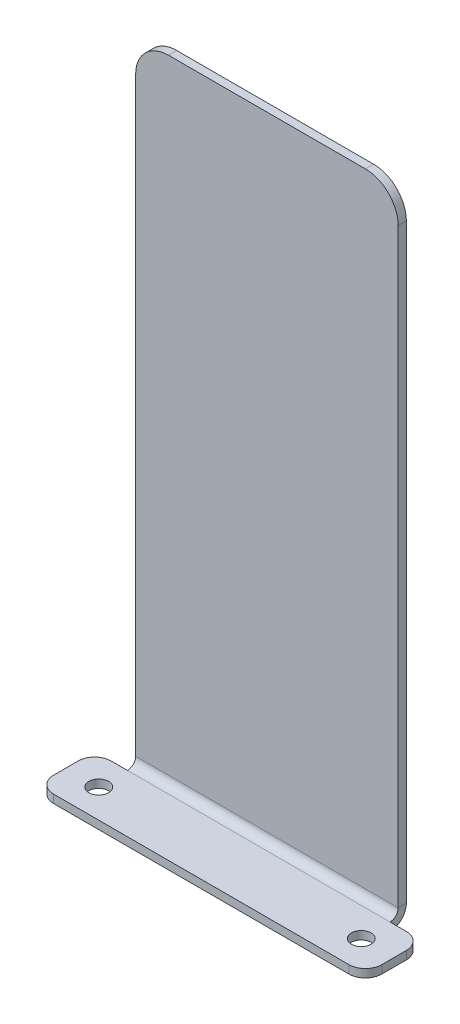
SolidWorks part; units mm, degrees
note: The reader was unsure of these and kept them because the rebuilt part matched: thickness of "Base-Flange1", "Edge-Flange1", "Sheet-Metal1", "Sheet-Metal2", "Sheet-Metal3", "Sheet-Metal4"; flange length of "Edge-Flange1".
material "5052-H32"
ref_plane "Front Plane" through (0, 0, 0) normal (0, 0, 1) x (1, 0, 0)
ref_plane "Top Plane" through (0, 0, 0) normal (0, 1, 0) x (1, 0, 0)
ref_plane "Right Plane" through (0, 0, 0) normal (1, 0, 0) x (0, 0, -1)
sketch "Sketch1" plane through (0, 0, 0) normal (0, 0, 1) x (1, 0, 0)
  line L1 (-50.8, 0) -> (50.8, 0)
  line L2 (-50.8, 0) -> (-50.8, 247.65)
  line L3 (-50.8, 247.65) -> (50.8, 247.65)
  line L4 (50.8, 0) -> (50.8, 247.65)
  point P4 (0, 0)
  dimension "D1" = 101.6
  dimension "D2" = 247.65
base flange "Base-Flange1" sketch "Sketch1" thickness 3.175 reverse thickness direction no parameters "D1"=3.175
edge flange "Edge-Flange1" sketch "Sketch8" flange angle 90 flange length 25.4 flange position material inside bend radius 3.175 thickness 3.175 relief rectangular parameters "D1"=3.9688, "D6"=10
sketch "Sketch8" plane through (0, 0, 0) normal (0, -1, 0) x (1, 0, 0)
  line L0 (-50.8, 0) -> (50.8, 0) construction
  line L1 (-50.8, 0) -> (50.8, 0)
  line L2 (-50.8, 0) -> (-50.8, 25.4)
  line L3 (-50.8, 25.4) -> (50.8, 25.4)
  line L4 (50.8, 25.4) -> (50.8, 0)
bend "EdgeBend1" bend radius 3.175 bend angle 90 parameters "D5"=1
fillet "Fillet1" radius 12.7 2 edges at (-50.8, 247.65, -1.5875) (50.8, 247.65, -1.5875)
sketch "Sketch9" plane through (0, 3.175, 0) normal (0, 1, 0) x (1, 0, 0)
  line L0 (-50.8, -3.175) -> (50.8, -3.175) construction
  line L1 (-63.5, -25.4) -> (63.5, -25.4)
  line L2 (-63.5, -25.4) -> (-63.5, -3.175)
  line L3 (-63.5, -3.175) -> (63.5, -3.175)
  line L4 (63.5, -25.4) -> (63.5, -3.175)
  line L5 (50.8, -25.4) -> (-50.8, -25.4) construction
  line L6 (-50.8, -25.4) -> (-50.8, -3.175) construction
  point P8 (0, -25.4)
  dimension "D1" = 12.7
extrude "Boss-Extrude1" add sketch "Sketch9" against normal up to surface (3.175 mm away) up to face at (0, 0, 14.2875)
sketch "Sketch10" plane through (0, 3.175, 0) normal (0, 1, 0) x (1, 0, 0)
  line L0 (-50.8, -14.2875) -> (50.8, -14.2875) construction
  line L1 (-50.8, -3.175) -> (-63.5, -3.175) construction
  point P2 (0, -14.2875)
  dimension "D1" = 11.1125
  dimension "D2" = 101.6
hole_wizard "1/4 Clearance Hole1" positions "Sketch11" profile "Sketch12" hole size "1/4" standard "ANSI Inch" end condition through all
sketch "Sketch11" plane through (0, 3.175, 0) normal (0, 1, 0) x (1, 0, 0)
  point P0 (-50.8, -14.2875)
  point P3 (50.8, -14.2875)
sketch "Sketch12" plane through (-50.8, 3.175, 14.2875) normal (1, 0, 0) x (0, 0, 1)
  line L0 (0, 0) -> (0, 3.175)
  line L1 (0, 3.175) -> (3.81, 3.175)
  line L2 (3.81, 3.175) -> (3.81, 0)
  line L5 (3.81, 0) -> (0, 0)
  line L11 (0, -6.35) -> (0, 107.95) construction
  dimension "Thru Hole Dia." = 7.62
  dimension "Thru Hole Depth" = 3.175
fillet "Fillet3" radius 6.35 4 edges at (-63.5, 1.5875, 3.175) (-63.5, 1.5875, 25.4) (63.5, 1.5875, 3.175) (63.5, 1.5875, 25.4)
sketch "Bend-Lines1" [suppressed] plane through (0, 0, 0) normal (0, 1, 0) x (1, 0, 0)
sketch "Bounding-Box1" [suppressed] plane through (0, 0, 0) normal (0, 1, 0) x (1, 0, 0)
sheet metal parameters "Sheet-Metal1" thickness 3.175 parameters "D1"=2.9766, "D7"=1.9844
flat pattern "Flat-Pattern1" [suppressed]
sketch "Bend-Lines2" plane through (0, 0, 0) normal (0, 1, 0) x (1, 0, 0)
sketch3d "Bounding-Box2" [suppressed]
  line L0 (-50.8, 241.3, 0) -> (-50.8, 0, 0) construction
  line L1 (50.8, 241.3, 0) -> (50.8, 0, 0) construction
  line L2 (-50.8, 241.3, 0) -> (50.8, 241.3, 0) construction
  line L3 (-50.8, 0, 0) -> (50.8, 0, 0) construction
sheet metal parameters "Sheet-Metal2" thickness 3.175 parameters "D1"=2.9766, "D7"=1.9844
flat pattern "Flat-Pattern1"
sketch "Bend-Lines2" plane through (0, 0, 0) normal (0, 0, 1) x (1, 0, 0)
  line L0 (-50.8, 1.8439) -> (50.8, 1.8439) construction
  line L1 (-50.8, 1.8439) -> (50.8, 1.8439) construction
sketch3d "Bounding-Box2" [suppressed]
  line L0 (50.8, -36.3966, 0) -> (50.8, 247.65, 0) construction
  line L1 (-50.8, -36.3966, 0) -> (-50.8, 247.65, 0) construction
  line L2 (50.8, -36.3966, 0) -> (-50.8, -36.3966, 0) construction
  line L3 (50.8, 247.65, 0) -> (-50.8, 247.65, 0) construction
bend of the flat pattern "Flatten-<EdgeBend1>1"
sheet metal parameters "Sheet-Metal3" thickness 3.175 parameters "D1"=2.9766, "D7"=1.9844
flat pattern "Flat-Pattern1"
sketch "Bend-Lines2" plane through (0, 0, 0) normal (0, 0, 1) x (1, 0, 0)
  line L0 (-50.8, 1.8439) -> (50.8, 1.8439) construction
  line L1 (-50.8, 1.8439) -> (50.8, 1.8439) construction
sketch3d "Bounding-Box2" [suppressed]
  line L0 (76.2, -36.3966, 0) -> (76.2, 247.65, 0) construction
  line L1 (-76.2, -36.3966, 0) -> (-76.2, 247.65, 0) construction
  line L2 (76.2, -36.3966, 0) -> (-76.2, -36.3966, 0) construction
  line L3 (76.2, 247.65, 0) -> (-76.2, 247.65, 0) construction
bend of the flat pattern "Flatten-<EdgeBend1>1"
sheet metal parameters "Sheet-Metal4" thickness 3.175 parameters "D1"=2.9766, "D7"=1.9844
flat pattern "Flat-Pattern1" [suppressed]
sketch "Bend-Lines2" plane through (0, 0, 0) normal (0, 0, 1) x (1, 0, 0)
  line L0 (-50.8, 2.6095) -> (50.8, 2.6095) construction
  line L1 (-50.8, 2.6095) -> (50.8, 2.6095) construction
sketch3d "Bounding-Box2" [suppressed]
  line L0 (63.5, -23.3559, 0) -> (63.5, 247.65, 0) construction
  line L1 (-63.5, -23.3559, 0) -> (-63.5, 247.65, 0) construction
  line L2 (63.5, -23.3559, 0) -> (-63.5, -23.3559, 0) construction
  line L3 (63.5, 247.65, 0) -> (-63.5, 247.65, 0) construction
bend of the flat pattern "Flatten-<EdgeBend1>1"
sketch "Sketch10-1" plane through (0, 2.0441, 0) normal (0, 0, 1) x (1, 0, 0)
  line L0 (-50.8, -14.2875) -> (50.8, -14.2875) construction
  line L1 (127, -3.175) -> (-63.5, -3.175) construction
  dimension "D1" = 11.1125
  dimension "D2" = 101.6
